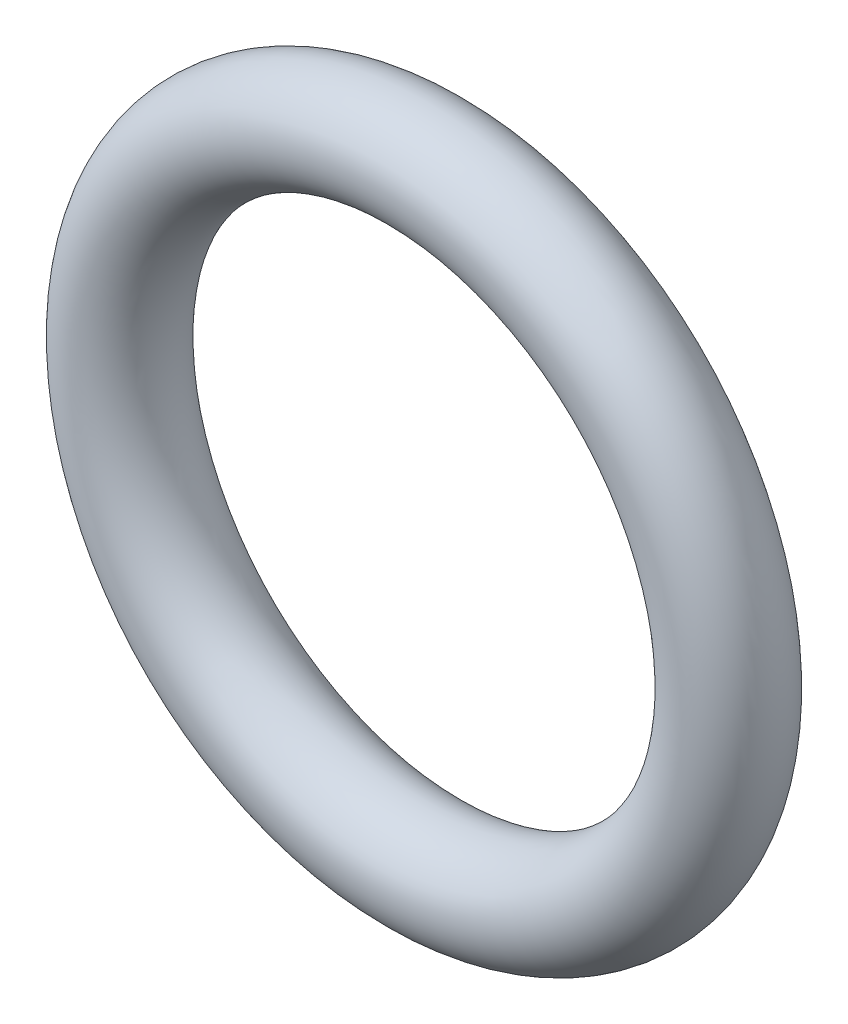
SolidWorks part; units mm, degrees
ref_plane "Front Plane" through (0, 0, 0) normal (0, 0, 1) x (1, 0, 0)
ref_plane "Top Plane" through (0, 0, 0) normal (0, 1, 0) x (1, 0, 0)
ref_plane "Right Plane" through (0, 0, 0) normal (1, 0, 0) x (0, 0, -1)
sketch "Sketch1" plane through (0, 0, 0) normal (1, 0, 0) x (0, 0, -1)
  circle A0 centre (0, 0) radius 2.282
  dimension "D1" = 4.5641
sketch "Sketch2" plane through (0, 0, 0) normal (0, 0, 1) x (1, 0, 0)
  circle A0 centre (0, -13.3945) radius 13.3945
  point P3 (0, 0)
  dimension "D1" = 26.7891
sweep "Sweep1" add profiles "Sketch1" path "Sketch2"
